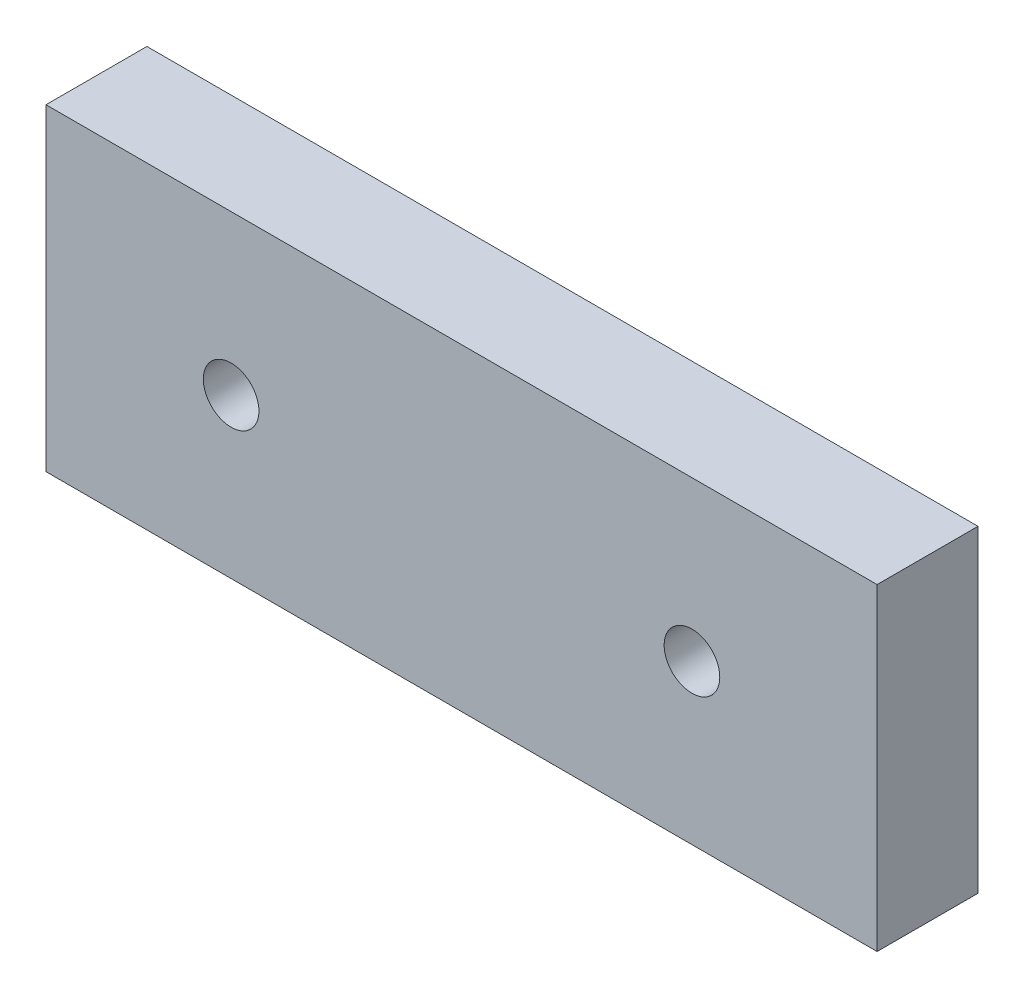
SolidWorks part; units mm, degrees
ref_plane "Front Plane" through (0, 0, 0) normal (0, 0, 1) x (1, 0, 0)
ref_plane "Top Plane" through (0, 0, 0) normal (0, 1, 0) x (1, 0, 0)
ref_plane "Right Plane" through (0, 0, 0) normal (1, 0, 0) x (0, 0, -1)
sketch "Sketch1" plane through (0, 0, 0) normal (0, 0, 1) x (1, 0, 0)
  line L0 (11.65, 10) -> (40.65, 10) construction
  line L1 (0, 0) -> (52.3, 0)
  line L2 (0, 0) -> (0, 20)
  line L3 (0, 20) -> (52.3, 20)
  line L4 (52.3, 0) -> (52.3, 20)
  circle A0 centre (11.65, 10) radius 1.75
  circle A1 centre (40.65, 10) radius 1.75
  point P9 (52.3, 10)
  point P10 (26.15, 10)
  point P11 (26.15, 20)
  point P12 (51.3707, 0)
  dimension "D4" = 3.5
  dimension "D1" = 29
  dimension "D2" = 20
  dimension "D3" = 52.3
extrude "Boss-Extrude1" add sketch "Sketch1" along normal blind 6.35
